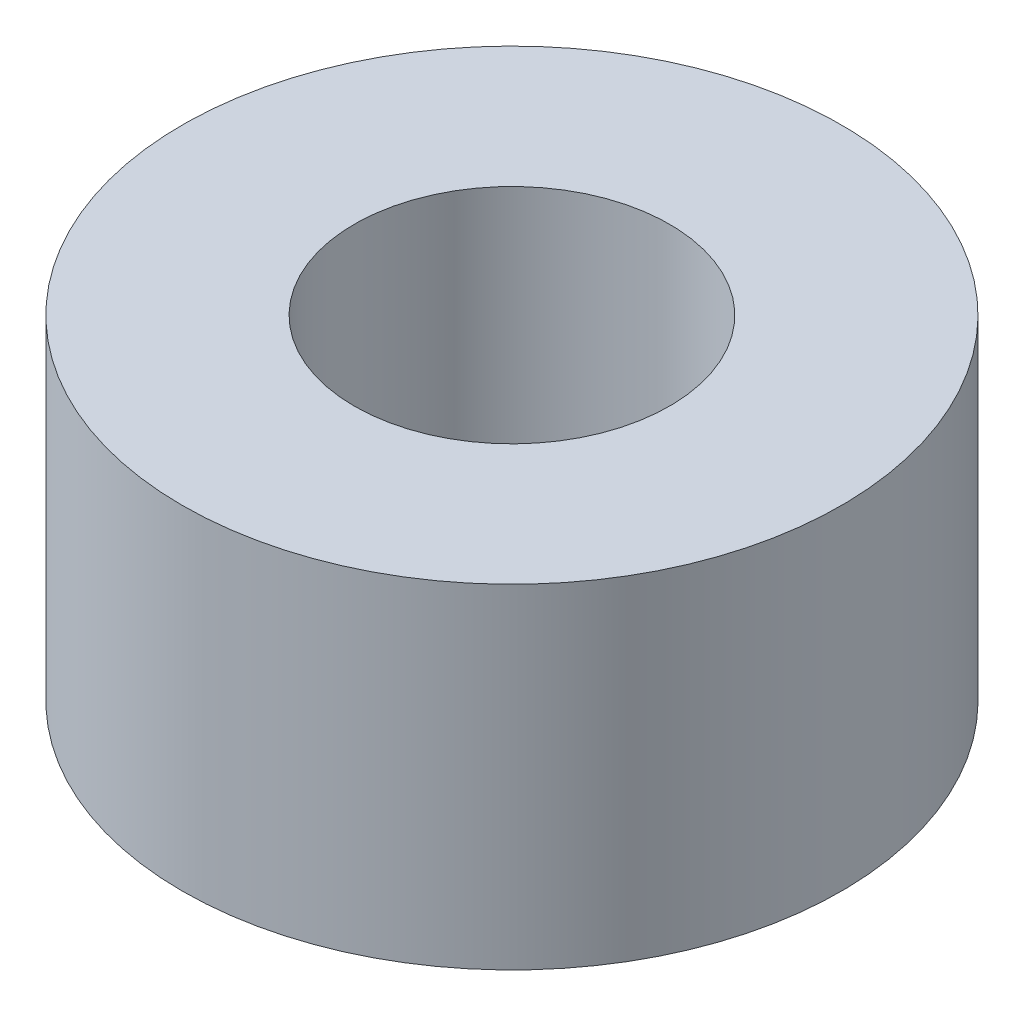
SolidWorks part; units mm, degrees
ref_plane "Front Plane" through (0, 0, 0) normal (0, 0, 1) x (1, 0, 0)
ref_plane "Top Plane" through (0, 0, 0) normal (0, 1, 0) x (1, 0, 0)
ref_plane "Right Plane" through (0, 0, 0) normal (1, 0, 0) x (0, 0, -1)
sketch "Sketch1" plane through (0, 0, 0) normal (0, 1, 0) x (1, 0, 0)
  circle A0 centre (0, 0) radius 15
  dimension "SLEEVE_OD" = 30
extrude "Boss-Extrude1" add sketch "Sketch1" along normal blind 15.2037
sketch "Sketch2" plane through (0, 0, 0) normal (0, 1, 0) x (1, 0, 0)
  circle A0 centre (0, 0) radius 7.1738
  dimension "BORE_D" = 14.3477
extrude "Cut-Extrude1" cut sketch "Sketch2" along normal through all
chamfer "Chamfer1" distance 2.7945 angle 64.194 rebuild error yes
